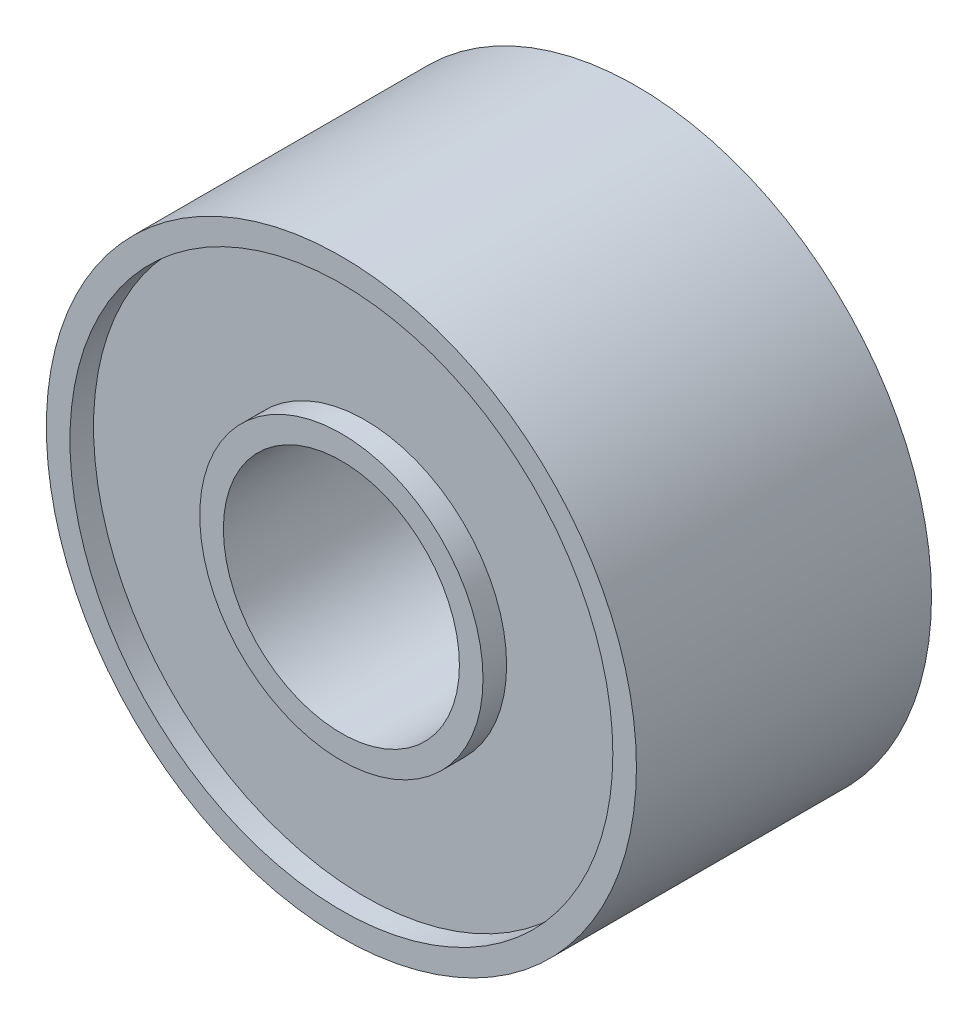
SolidWorks part; units mm, degrees
ref_plane "前视基准面" through (0, 0, 0) normal (0, 0, 1) x (1, 0, 0)
ref_plane "上视基准面" through (0, 0, 0) normal (0, 1, 0) x (1, 0, 0)
ref_plane "右视基准面" through (0, 0, 0) normal (1, 0, 0) x (0, 0, -1)
sketch "草图1" plane through (0, 0, 0) normal (0, 0, 1) x (1, 0, 0)
  circle A0 centre (0, 0) radius 2.5
  circle A1 centre (0, 0) radius 1
  dimension "D1" = 2
  dimension "D2" = 5
extrude "凸台-拉伸1" add sketch "草图1" along normal blind 1.25 and the other way blind 1.25
sketch "草图2" plane through (0, 0, 1.25) normal (0, 0, 1) x (1, 0, 0)
  circle A2 centre (0, 0) radius 2.3
  circle A3 centre (0, 0) radius 2.3
  circle A5 centre (0, 0) radius 1.2
  circle A6 centre (0, 0) radius 1.2
  dimension "D1" = 0.2
  dimension "D2" = 0.2
extrude "切除-拉伸1" cut sketch "草图2" against normal blind 0.2
mirror "镜向1" about plane through (0, 0, 0) normal (0, 0, 1) of "切除-拉伸1"
